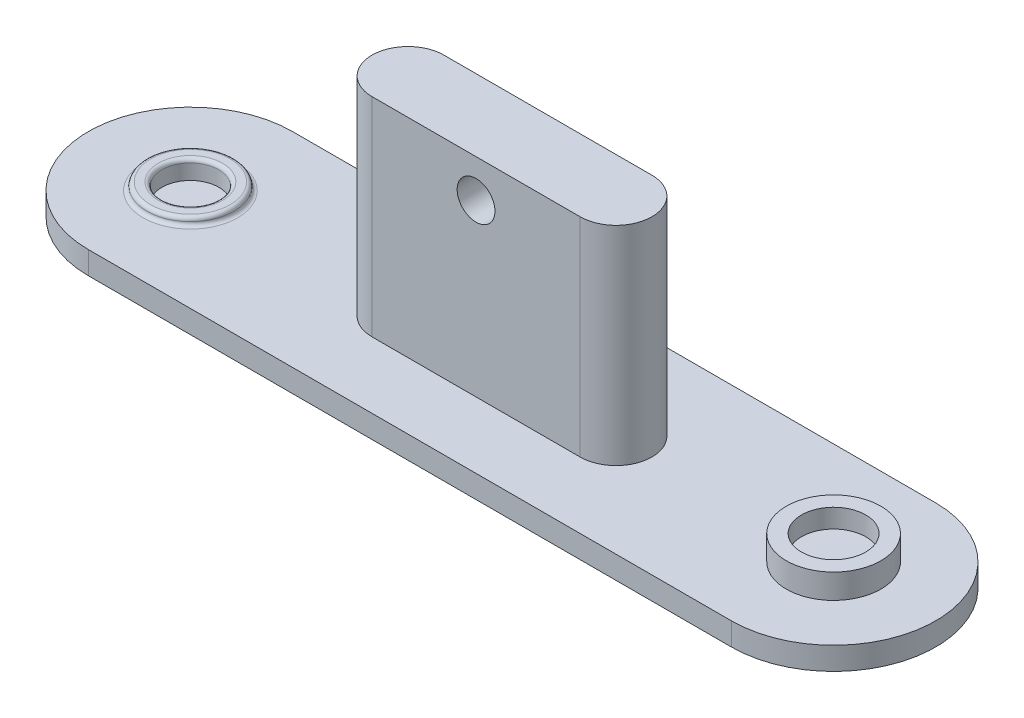
SolidWorks part; units mm, degrees
ref_plane "Front Plane" through (0, 0, 0) normal (0, 0, 1) x (1, 0, 0)
ref_plane "Top Plane" through (0, 0, 0) normal (0, 1, 0) x (1, 0, 0)
ref_plane "Right Plane" through (0, 0, 0) normal (1, 0, 0) x (0, 0, -1)
sketch "Sketch1" plane through (0, 0, 0) normal (0, 1, 0) x (1, 0, 0)
  line L0 (-142.4958, 0) -> (136.0591, 0) construction
  line L1 (0, 82.9006) -> (0, -67.1417) construction
  line L2 (-42.5, -13.5) -> (42.5, -13.5)
  line L3 (-42.5, 13.5) -> (42.5, 13.5)
  arc A0 (-42.5, 13.5) -> (-42.5, -13.5) centre (-42.5, 0) ccw
  arc A1 (42.5, 13.5) -> (42.5, -13.5) centre (42.5, 0) cw
  dimension "D1" = 85
  dimension "D2" = 27
extrude "Boss-Extrude1" add sketch "Sketch1" along normal blind 3
sketch "Sketch7" plane through (0, 3, 0) normal (0, 1, 0) x (1, 0, 0)
  circle A0 centre (-42.5, 0) radius 5.75
  arc A1 (-42.5, 13.5) -> (-42.5, -13.5) centre (-42.5, 0) ccw construction
  dimension "D1" = 11.5
extrude "Boss-Extrude5" add sketch "Sketch7" along normal blind 1
sketch "Sketch2" plane through (0, 4, 0) normal (0, 1, 0) x (1, 0, 0)
  circle A0 centre (-42.5, 0) radius 3.75
  arc A1 (-42.5, 13.5) -> (-42.5, -13.5) centre (-42.5, 0) ccw construction
  dimension "D1" = 7.5
extrude "Cut-Extrude1" cut sketch "Sketch2" against normal blind 2.5
sketch "Sketch3" plane through (0, 3, 0) normal (0, 1, 0) x (1, 0, 0)
  circle A0 centre (42.5, 0) radius 6.25
  arc A1 (42.5, -13.5) -> (42.5, 13.5) centre (42.5, 0) ccw construction
  dimension "D1" = 12.5
extrude "Boss-Extrude3" add sketch "Sketch3" along normal blind 3.25
sketch "Sketch4" plane through (0, 6.25, 0) normal (0, 1, 0) x (1, 0, 0)
  circle A0 centre (42.5, 0) radius 4.25
  circle A1 centre (42.5, 0) radius 6.25 construction
  dimension "D1" = 8.5
extrude "Cut-Extrude2" cut sketch "Sketch4" against normal blind 2.5
sketch "Sketch5" plane through (0, 3, 0) normal (0, 1, 0) x (1, 0, 0)
  line L0 (0, 28.1167) -> (0, -35.5844) construction
  line L1 (-13.75, 4.75) -> (13.75, 4.75)
  line L2 (-13.75, -4.75) -> (13.75, -4.75)
  arc A0 (-13.75, 4.75) -> (-13.75, -4.75) centre (-13.75, 0) ccw
  arc A1 (13.75, 4.75) -> (13.75, -4.75) centre (13.75, 0) cw
  dimension "D1" = 27.5
  dimension "D2" = 9.5
extrude "Boss-Extrude4" add sketch "Sketch5" along normal blind 27.5
sketch "Sketch6" plane through (0, 0, -4.75) normal (0, 0, -1) x (-1, 0, 0)
  line L2 (-13.75, 30.5) -> (13.75, 30.5) construction
  line L3 (0, -7.6238) -> (0, 35.8367) construction
  circle A0 centre (0, 25.5) radius 2.5
  dimension "D1" = 5
  dimension "D2" = 5
extrude "Cut-Extrude3" cut sketch "Sketch6" against normal through all
fillet "Fillet1" radius 0.5 3 edges at (-42.5, 4, 3.75) (-42.5, 4, 5.75) (-42.5, 3, 5.75)
